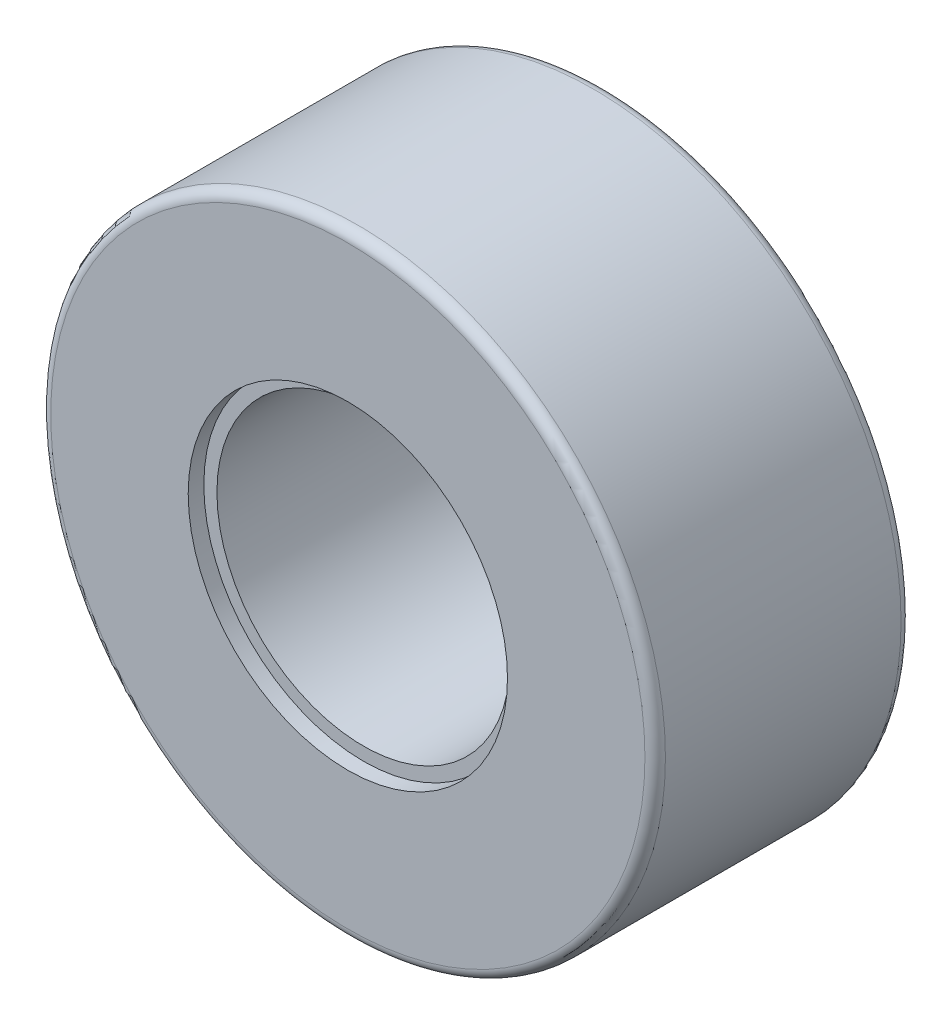
SolidWorks part; units mm, degrees
material "PETG"
ref_plane "Front Plane" through (0, 0, 0) normal (0, 0, 1) x (1, 0, 0)
ref_plane "Top Plane" through (0, 0, 0) normal (0, 1, 0) x (1, 0, 0)
ref_plane "Right Plane" through (0, 0, 0) normal (1, 0, 0) x (0, 0, -1)
sketch "Sketch1" plane through (0, 0, 0) normal (0, 0, 1) x (1, 0, 0)
  circle A0 centre (0, 0) radius 14.3025
  circle A1 centre (0, 0) radius 30
  dimension "D1" = 60
  dimension "D2" = 28.605
extrude "Boss-Extrude1" add sketch "Sketch1" along normal mid plane 25
sketch "Sketch3" plane through (0, 0, 12.5) normal (0, 0, 1) x (1, 0, 0)
  circle A0 centre (0, 0) radius 15.5825
  dimension "D1" = 31.165
extrude "Cut-Extrude1" cut sketch "Sketch3" against normal blind 1.524
mirror "Mirror1" about plane through (0, 0, 0) normal (0, 0, 1) of "Cut-Extrude1"
fillet "Fillet1" radius 1 2 edges at (30, 0, -12.5) (30, 0, 12.5)
equation "\"tol_dia_id_intfc\" = 0.0200mm ' For hole diameters - Interference fit"
equation "\"tol_dia_id_slip\"  = 0.0300mm ' For hole diameters - Slip fit"
equation "\"tol_dia_id_clear\" = 0.0500mm ' For hole diameters - Clearance fit"
equation "\"tol_dia_od_intfc\" = 0.0200mm ' For shaft diameters - Interference fit"
equation "\"tol_dia_od_slip\"  = 0.0300mm ' For shaft diameters - Slip fit"
equation "\"tol_dia_od_clear\" = 0.0500mm ' For shaft diameters - Clearance fit"
equation "\"tol_general_intfc\"= 0.0030mm ' For general parts (Horiz) - Interference fit"
equation "\"tol_general_slip\" = 0.0050mm ' For general parts (Horiz) - Slip fit"
equation "\"tol_general_clear\"= 0.0100mm ' For general parts (Horiz) - Clearance fit"
equation "\"tol_layer_intfc\"  = 0.0030mm ' For all parts (Vert) - Interference fit"
equation "\"tol_layer_slip\"   = 0.0050mm ' For all parts (Vert) - Slip fit"
equation "\"tol_layer_clear\"  = 0.0100mm ' For all parts (Vert) - Clearance fit"
equation "\"tol_corner_rad\"   = 0.100mm ' For corners that fit into other parts"
equation "\"D2@Sketch1\"=1.125in + \"tol_dia_id_slip\""
equation "\"D1@Sketch3\"=1.225in + \"tol_dia_id_clear\""
